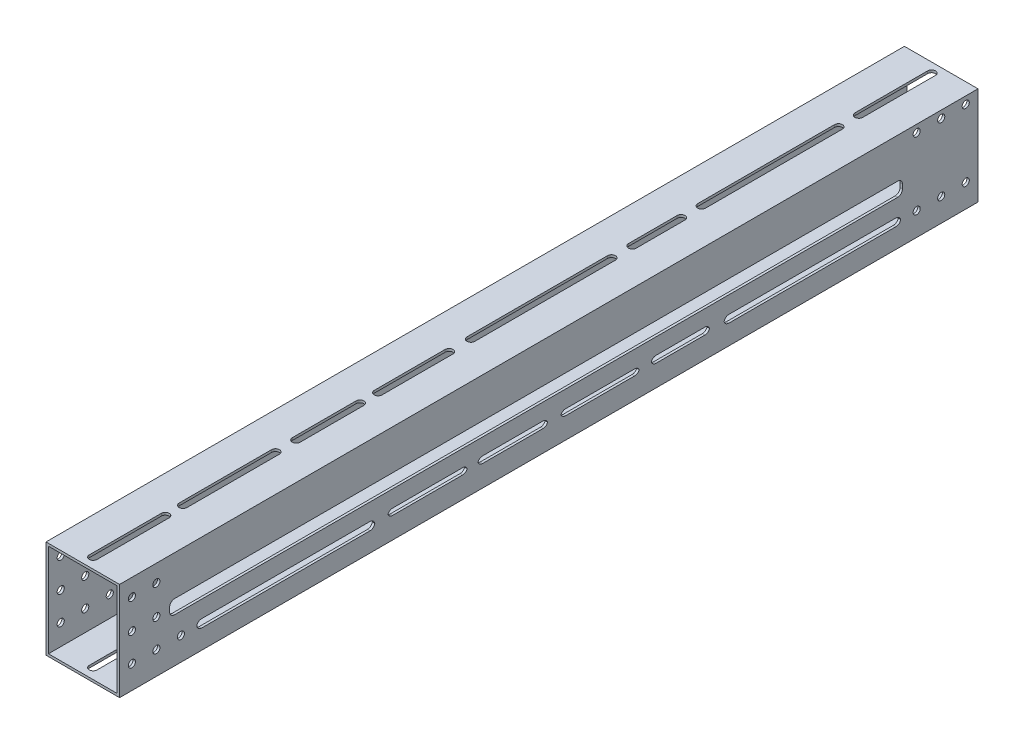
SolidWorks part; units mm, degrees
material "6061 合金"
ref_plane "前视基准面" through (0, 0, 0) normal (0, 0, 1) x (1, 0, 0)
ref_plane "上视基准面" through (0, 0, 0) normal (0, 1, 0) x (1, 0, 0)
ref_plane "右视基准面" through (0, 0, 0) normal (1, 0, 0) x (0, 0, -1)
sketch "草图4" plane through (0, 0, 0) normal (0, 0, 1) x (1, 0, 0)
  line L1 (-15, -20) -> (15, -20)
  line L2 (-15, -20) -> (-15, 20)
  line L3 (-15, 20) -> (15, 20)
  line L4 (15, -20) -> (15, 20)
  line L5 (-15, -20) -> (15, 20) construction
  line L6 (-15, 20) -> (15, -20) construction
  line L7 (-14, -19) -> (14, -19)
  line L8 (-14, -19) -> (-14, 19)
  line L9 (-14, 19) -> (14, 19)
  line L10 (14, -19) -> (14, 19)
  line L11 (-14, -19) -> (14, 19) construction
  line L12 (-14, 19) -> (14, -19) construction
  point P0 (0, 0)
  point P6 (0, 0)
  dimension "D1" = 30
  dimension "D2" = 40
  dimension "D3" = 1
  dimension "D4" = 1
extrude "凸台-拉伸1" add sketch "草图4" along normal blind 350
sketch "草图5" plane through (0, 0, 0) normal (0, 0, 1) x (1, 0, 0)
  line L0 (0, 19) -> (0, -19) construction
  line L1 (14, 19) -> (-14, 19) construction
  line L2 (-14, -19) -> (14, -19) construction
  line L3 (15, 20) -> (-15, 20) construction
  line L4 (-10, 15) -> (10, 15)
  line L5 (-10, 15) -> (-10, -5)
  line L6 (-10, -5) -> (10, -5)
  line L7 (10, 15) -> (10, -5)
  line L8 (-10, 15) -> (10, -5) construction
  line L9 (-10, -5) -> (10, 15) construction
  line L10 (0, -5) -> (0, -7)
  line L11 (-20, -34) -> (20, -34) construction
  line L12 (-20, -35) -> (20, -35)
  line L13 (-20, -35) -> (-20, 25)
  line L14 (-20, 25) -> (20, 25)
  line L15 (20, -35) -> (20, 25)
  line L16 (-20, -35) -> (20, 25) construction
  line L17 (-20, 25) -> (20, -35) construction
  line L18 (0, -34) -> (0, -32)
  point P6 (0, 5)
  point P15 (0, -5)
  dimension "D1" = 15
  dimension "D2" = 20
  dimension "D3" = 20
  dimension "D4" = 2
  dimension "D5" = 40
  dimension "D6" = 60
  dimension "D7" = 5
  dimension "D8" = 1
  dimension "D9" = 2
sketch "草图6" plane through (0, 0, 0) normal (1, 0, 0) x (0, 0, -1)
  line L0 (0, -20) -> (0, 20) construction
  line L1 (-350, -20) -> (0, -20) construction
  line L2 (-175, 20) -> (-175, -20) construction
  line L3 (-350, 20) -> (0, 20) construction
  line L4 (-350, -20) -> (-350, 20) construction
  circle A0 centre (-5, -10.5) radius 1.45
  circle A1 centre (-15, -10.5) radius 1.45
  circle A3 centre (-25, -10.5) radius 1.45
  circle A4 centre (-345, -10.5) radius 1.45
  circle A5 centre (-335, -10.5) radius 1.45
  circle A6 centre (-325, -10.5) radius 1.45
  circle A7 centre (-345, 13) radius 1.45
  circle A8 centre (-335, 13) radius 1.45
  circle A9 centre (-345, 1) radius 1.45
  circle A10 centre (-335, 1) radius 1.45
  dimension "D1" = 5
  dimension "D2" = 9.5
  dimension "D3" = 2.9
  dimension "D4" = 15
  dimension "D5" = 10
  dimension "D7" = 9.5
  dimension "D8" = 9.5
  dimension "D13" = 10
  dimension "D14" = 7
  dimension "D15" = 2.9
  dimension "D16" = 12
  dimension "D17" = 5
  dimension "D19" = 10
  dimension "D20" = 12
  dimension "D10" = 7
  dimension "D11" = 5
extrude "切除-拉伸1" cut sketch "草图6" against normal mid plane 57
sketch "草图11" plane through (-15, 0, 0) normal (-1, 0, 0) x (0, 0, 1)
  line L0 (0, 17) -> (350, 17) construction
  line L1 (0, 20) -> (0, -20) construction
  line L2 (350, 20) -> (350, -20) construction
  line L3 (5, -10.5) -> (5, 17) construction
  line L4 (350, 20) -> (0, 20) construction
  line L5 (15, -10.5) -> (15, 17) construction
  line L6 (25, -10.5) -> (25, 17) construction
  circle A0 centre (5, 17) radius 1.45
  circle A1 centre (15, 17) radius 1.45
  circle A2 centre (25, 17) radius 1.45
  dimension "D2" = 2.9
  dimension "D1" = 3
extrude "切除-拉伸2" cut sketch "草图11" against normal through all
sketch "草图13" plane through (15, 0, 0) normal (1, 0, 0) x (0, 0, -1)
  line L1 (-329.5886, 3.7625) -> (-30.7851, 3.7625)
  line L2 (-329.5886, 3.7625) -> (-329.5886, -1.9291)
  line L3 (-329.5886, -1.9291) -> (-30.7851, -1.9291)
  line L4 (-30.7851, 3.7625) -> (-30.7851, -1.9291)
  line L9 (-318.5729, -8.8302) -> (-245.9066, -8.8302)
  line L10 (-318.5729, -8.8302) -> (-318.5729, -12.1201)
  line L11 (-318.5729, -12.1201) -> (-245.9066, -12.1201)
  line L12 (-245.9066, -8.8302) -> (-245.9066, -12.1201)
  line L13 (-240.695, -8.7274) -> (-208.1458, -8.7274)
  line L14 (-240.695, -8.7274) -> (-240.695, -11.287)
  line L15 (-240.695, -11.287) -> (-208.1458, -11.287)
  line L16 (-208.1458, -8.7274) -> (-208.1458, -11.287)
  line L17 (-204.0023, -11.2961) -> (-175.3689, -11.2961)
  line L18 (-204.0023, -11.2961) -> (-204.0023, -8.6193)
  line L19 (-204.0023, -8.6193) -> (-175.3689, -8.6193)
  line L20 (-175.3689, -11.2961) -> (-175.3689, -8.6193)
  line L21 (-170.1686, -8.9041) -> (-137.988, -8.9041)
  line L22 (-170.1686, -8.9041) -> (-170.1686, -11.37)
  line L23 (-170.1686, -11.37) -> (-137.988, -11.37)
  line L24 (-137.988, -8.9041) -> (-137.988, -11.37)
  line L25 (-133.284, -8.478) -> (-109.3675, -8.478)
  line L26 (-133.284, -8.478) -> (-133.284, -11.2647)
  line L27 (-133.284, -11.2647) -> (-109.3675, -11.2647)
  line L28 (-109.3675, -8.478) -> (-109.3675, -11.2647)
  line L29 (-103.5814, -8.8671) -> (-31.4615, -8.8671)
  line L30 (-103.5814, -8.8671) -> (-103.5814, -11.9538)
  line L31 (-103.5814, -11.9538) -> (-31.4615, -11.9538)
  line L32 (-31.4615, -8.8671) -> (-31.4615, -11.9538)
extrude "切除-拉伸3" cut sketch "草图13" against normal through all
sketch "草图14" plane through (0, 20, 0) normal (0, 1, 0) x (1, 0, 0)
  line L0 (0, 0) -> (0, -350) construction
  line L1 (15, -350) -> (-15, -350) construction
  line L2 (0, -3.9056) -> (0, -33.5822) construction
  line L3 (1.6, -3.9056) -> (1.6, -33.5822)
  line L4 (-1.6, -3.9056) -> (-1.6, -33.5822)
  line L5 (0, -41.8739) -> (0, -97.6781) construction
  line L6 (1.6, -41.8739) -> (1.6, -97.6781)
  line L7 (-1.6, -41.8739) -> (-1.6, -97.6781)
  line L8 (0, -106.0644) -> (0, -125.9479) construction
  line L9 (1.6, -106.0644) -> (1.6, -125.9479)
  line L10 (-1.6, -106.0644) -> (-1.6, -125.9479)
  line L11 (0, -134.425) -> (0, -191.7595) construction
  line L12 (1.6, -134.425) -> (1.6, -191.7595)
  line L13 (-1.6, -134.425) -> (-1.6, -191.7595)
  line L14 (0, -200.6456) -> (0, -229.586) construction
  line L15 (1.6, -200.6456) -> (1.6, -229.586)
  line L16 (-1.6, -200.6456) -> (-1.6, -229.586)
  line L17 (0, -236.999) -> (0, -262.9742) construction
  line L18 (1.6, -236.999) -> (1.6, -262.9742)
  line L19 (-1.6, -236.999) -> (-1.6, -262.9742)
  line L20 (0, -271.4238) -> (0, -309.1242) construction
  line L21 (1.6, -271.4238) -> (1.6, -309.1242)
  line L22 (-1.6, -271.4238) -> (-1.6, -309.1242)
  line L23 (0, -316.3685) -> (0, -345.7709) construction
  line L24 (1.6, -316.3685) -> (1.6, -345.7709)
  line L25 (-1.6, -316.3685) -> (-1.6, -345.7709)
  arc A0 (1.6, -3.9056) -> (-1.6, -3.9056) centre (0, -3.9056) ccw
  arc A1 (-1.6, -33.5822) -> (1.6, -33.5822) centre (0, -33.5822) ccw
  arc A2 (1.6, -41.8739) -> (-1.6, -41.8739) centre (0, -41.8739) ccw
  arc A3 (-1.6, -97.6781) -> (1.6, -97.6781) centre (0, -97.6781) ccw
  arc A4 (1.6, -106.0644) -> (-1.6, -106.0644) centre (0, -106.0644) ccw
  arc A5 (-1.6, -125.9479) -> (1.6, -125.9479) centre (0, -125.9479) ccw
  arc A6 (1.6, -134.425) -> (-1.6, -134.425) centre (0, -134.425) ccw
  arc A7 (-1.6, -191.7595) -> (1.6, -191.7595) centre (0, -191.7595) ccw
  arc A8 (1.6, -200.6456) -> (-1.6, -200.6456) centre (0, -200.6456) ccw
  arc A9 (-1.6, -229.586) -> (1.6, -229.586) centre (0, -229.586) ccw
  arc A10 (1.6, -236.999) -> (-1.6, -236.999) centre (0, -236.999) ccw
  arc A11 (-1.6, -262.9742) -> (1.6, -262.9742) centre (0, -262.9742) ccw
  arc A12 (1.6, -271.4238) -> (-1.6, -271.4238) centre (0, -271.4238) ccw
  arc A13 (-1.6, -309.1242) -> (1.6, -309.1242) centre (0, -309.1242) ccw
  arc A14 (1.6, -316.3685) -> (-1.6, -316.3685) centre (0, -316.3685) ccw
  arc A15 (-1.6, -345.7709) -> (1.6, -345.7709) centre (0, -345.7709) ccw
  point P7 (0, -18.7439)
  point P12 (0, -69.776)
  point P19 (0, -116.0061)
  point P26 (0, -163.0922)
  point P33 (0, -215.1158)
  point P40 (0, -249.9866)
  point P47 (0, -290.274)
  point P54 (0, -331.0697)
  dimension "D1" = 3.2
  dimension "D2" = 3.2
  dimension "D3" = 3.2
  dimension "D4" = 3.2
  dimension "D5" = 3.2
  dimension "D6" = 3.2
  dimension "D7" = 3.2
  dimension "D8" = 3.2
extrude "切除-拉伸4" cut sketch "草图14" against normal through all
fillet "圆角1" radius 2 56 edges at (-14.5, -8.8671, 31.4615) (-14.5, -11.9538, 31.4615) (-14.5, -11.9538, 103.5814) (-14.5, -8.8671, 103.5814) (-14.5, -8.478, 109.3675) (-14.5, -11.2647, 109.3675) (-14.5, -11.2647, 133.284) (-14.5, -8.478, 133.284) (-14.5, -8.9041, 137.988) (-14.5, -11.37, 137.988) (-14.5, -11.37, 170.1686) (-14.5, -8.9041, 170.1686) (-14.5, -8.6193, 175.3689) (-14.5, -11.2961, 175.3689) (-14.5, -11.2961, 204.0023) (-14.5, -8.6193, 204.0023) (-14.5, -8.7274, 208.1458) (-14.5, -11.287, 208.1458) (-14.5, -11.287, 240.695) (-14.5, -8.7274, 240.695) (-14.5, -8.8302, 245.9066) (-14.5, -12.1201, 245.9066) (-14.5, -12.1201, 318.5729) (-14.5, -8.8302, 318.5729) (-14.5, 3.7625, 30.7851) (-14.5, -1.9291, 30.7851) (-14.5, 3.7625, 329.5886) (-14.5, -1.9291, 329.5886) (14.5, -8.8671, 103.5814) (14.5, -8.8671, 31.4615) (14.5, -11.9538, 31.4615) (14.5, -11.9538, 103.5814) (14.5, -8.478, 133.284) (14.5, -8.478, 109.3675) (14.5, -11.2647, 109.3675) (14.5, -11.2647, 133.284) (14.5, -8.9041, 170.1686) (14.5, -8.9041, 137.988) (14.5, -11.37, 137.988) (14.5, -11.37, 170.1686) (14.5, -8.6193, 204.0023) (14.5, -8.6193, 175.3689) (14.5, -11.2961, 175.3689) (14.5, -11.2961, 204.0023) (14.5, -8.7274, 240.695) (14.5, -8.7274, 208.1458) (14.5, -11.287, 208.1458) (14.5, -11.287, 240.695) (14.5, -8.8302, 245.9066) (14.5, -12.1201, 245.9066) (14.5, -12.1201, 318.5729) (14.5, 3.7625, 329.5886) (14.5, 3.7625, 30.7851) (14.5, -1.9291, 30.7851) (14.5, -1.9291, 329.5886) (14.5, -8.8302, 318.5729)
sketch "草图7" plane through (0, -19, 0) normal (0, 1, 0) x (1, 0, 0)
  line L0 (15, 0) -> (-15, 0) construction
  line L1 (-6, 0) -> (-3, 0)
  line L2 (-6, 0) -> (-6, -350)
  line L3 (-6, -350) -> (-3, -350)
  line L4 (-3, 0) -> (-3, -350)
  line L5 (15, -350) -> (-15, -350) construction
  line L6 (-15, -350) -> (-15, 0) construction
  line L7 (0, 0) -> (0, -350) construction
  line L8 (3, 0) -> (3, -350)
  line L9 (6, -350) -> (3, -350)
  line L10 (6, 0) -> (6, -350)
  line L11 (6, 0) -> (3, 0)
  dimension "D1" = 3
  dimension "D2" = 9
split line "分割线1"
split line "分割线2"
sketch "草图7<2>" plane through (0, -19, 0) normal (0, 1, 0) x (1, 0, 0) same geometry as "草图7"
sketch "草图8" plane through (14, 0, 0) normal (-1, 0, 0) x (0, 0, 1)
  line L0 (0, 20) -> (0, -20) construction
  line L1 (0, -4) -> (350, -4)
  line L2 (0, -4) -> (0, -7)
  line L3 (0, -7) -> (350, -7)
  line L4 (350, -4) -> (350, -7)
  line L5 (350, 20) -> (350, -20) construction
  line L6 (350, 20) -> (0, 20) construction
  line L7 (0, 9) -> (350, 9)
  line L8 (0, 9) -> (0, 6)
  line L9 (0, 6) -> (350, 6)
  line L10 (350, 9) -> (350, 6)
  line L11 (350, -20) -> (0, -20) construction
  dimension "D1" = 3
  dimension "D2" = 11
  dimension "D3" = 13
split line "分割线3"
split line "分割线4"
sketch "草图8<2>" plane through (14, 0, 0) normal (-1, 0, 0) x (0, 0, 1) same geometry as "草图8"
sketch "草图9" plane through (-15, 0, 0) normal (-1, 0, 0) x (0, 0, 1)
  line L0 (0, 20) -> (0, -20) construction
  line L1 (0, 16.5) -> (350, 16.5)
  line L2 (0, 16.5) -> (0, 13.5)
  line L3 (0, 13.5) -> (350, 13.5)
  line L4 (350, 16.5) -> (350, 13.5)
  line L5 (350, 20) -> (350, -20) construction
  line L6 (350, 20) -> (0, 20) construction
  line L7 (0, 0) -> (350, 0) construction
  line L8 (350, -16.5) -> (350, -13.5)
  line L9 (0, -13.5) -> (350, -13.5)
  line L10 (0, -16.5) -> (0, -13.5)
  line L11 (0, -16.5) -> (350, -16.5)
  dimension "D1" = 3.5
  dimension "D2" = 3
split line "分割线5"
split line "分割线6"
sketch "草图9<2>" plane through (-15, 0, 0) normal (-1, 0, 0) x (0, 0, 1) same geometry as "草图9"
sketch "草图10" plane through (0, -20, 0) normal (0, -1, 0) x (1, 0, 0)
  line L0 (0, 350) -> (0, 0) construction
  line L1 (-15, 350) -> (15, 350) construction
  line L2 (-15, 0) -> (15, 0) construction
  line L3 (-12, 350) -> (-9, 350)
  line L4 (-12, 350) -> (-12, 0)
  line L5 (-12, 0) -> (-9, 0)
  line L6 (-9, 350) -> (-9, 0)
  line L7 (-15, 350) -> (-15, 0) construction
  line L8 (9, 350) -> (9, 0)
  line L9 (12, 0) -> (9, 0)
  line L10 (12, 350) -> (12, 0)
  line L11 (12, 350) -> (9, 350)
  dimension "D1" = 3
  dimension "D2" = 3
split line "分割线7"
split line "分割线8"
sketch "草图10<2>" plane through (0, -20, 0) normal (0, -1, 0) x (1, 0, 0) same geometry as "草图10"
sketch "草图12" plane through (15, 0, 0) normal (1, 0, 0) x (0, 0, -1)
  line L0 (-330, -5.5) -> (-330, 13.5)
  line L2 (-330, 20) -> (-330, -5.5) construction
  line L3 (-330, -5.5) -> (-320, -5.5)
  line L4 (-320, -5.5) -> (-320, -15) construction
  line L5 (-320, -15) -> (-30, -15) construction
  line L6 (-30, -15) -> (-30, 20) construction
  line L7 (-350, 20) -> (0, 20) construction
  line L8 (-350, -20) -> (0, -20) construction
  line L9 (-333.5858, 13.5) -> (0, 13.5) construction
  line L10 (-320, -5.5) -> (-320, -13.5)
  line L11 (0, -13.5) -> (-350, -13.5) construction
  line L12 (-320, -13.5) -> (-30, -13.5)
  line L13 (-30, -13.5) -> (-30, 13.5)
  arc A0 (-23.5858, 16.5) -> (-26.4142, 16.5) centre (-25, 17) ccw construction
  circle A1 centre (-325, -10.5) radius 1.5 construction
  circle A2 centre (-335, 1) radius 1.5 construction
  dimension "D2" = 5
  dimension "D1" = 5
  dimension "D3" = 5
  dimension "D4" = 5
  dimension "D5" = 5
split line "分割线9"
split line "分割线10"
sketch "草图12<2>" plane through (15, 0, 0) normal (1, 0, 0) x (0, 0, -1) same geometry as "草图12"
